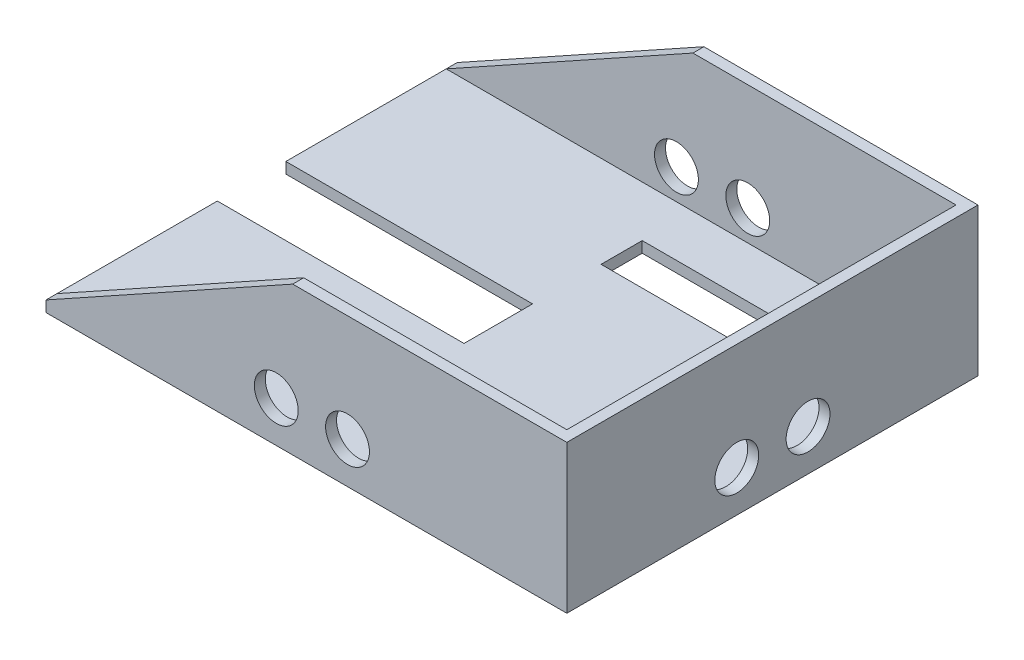
SolidWorks part; units mm, degrees
ref_plane "Front" through (0, 0, 0) normal (0, 0, 1) x (1, 0, 0)
ref_plane "Top" through (0, 0, 0) normal (0, 1, 0) x (1, 0, 0)
ref_plane "Right" through (0, 0, 0) normal (1, 0, 0) x (0, 0, -1)
sketch "Sketch1" plane through (0, 0, 0) normal (0, 1, 0) x (1, 0, 0)
  line L0 (-5, -12.5) -> (-5, 12.5)
  line L1 (95, -75) -> (-95, -75)
  line L2 (95, -75) -> (95, 75)
  line L3 (95, 75) -> (-95, 75)
  line L4 (-95, -75) -> (-95, -12.5)
  line L5 (0, 75) -> (0, -75) construction
  line L6 (95, 0) -> (-95, 0) construction
  line L7 (-5, 12.5) -> (-95, 12.5)
  line L8 (-5, -12.5) -> (-95, -12.5)
  line L9 (-95, 12.5) -> (-95, 75)
  point P0 (0, 0)
  point P4 (0, 0)
  point P7 (-5, 0)
  dimension "D1" = 190
  dimension "D2" = 150
  dimension "D3" = 25
  dimension "D4" = 100
extrude "Boss-Extrude1" add sketch "Sketch1" along normal blind 4
sketch "Sketch2" plane through (0, 0, 75) normal (0, 0, 1) x (1, 0, 0)
  line L0 (95, 4) -> (95, 54)
  line L1 (95, 54) -> (-5, 54)
  line L2 (-5, 54) -> (-95, 4)
  line L3 (-95, 4) -> (95, 4)
  dimension "D1" = 50
  dimension "D2" = 100
extrude "Boss-Extrude2" add sketch "Sketch2" against normal blind 4
mirror "Mirror1" about plane through (0, 0, 0) normal (0, 0, 1) of "Boss-Extrude2"
sketch "Sketch3" plane through (95, 0, 0) normal (1, 0, 0) x (0, 0, -1)
  line L0 (-71, 54) -> (71, 54)
  line L1 (71, 4) -> (71, 54) construction
  line L2 (71, 54) -> (71, 4)
  line L3 (71, 4) -> (-71, 4)
  line L4 (-71, 4) -> (-71, 54)
extrude "Boss-Extrude3" add sketch "Sketch3" against normal blind 4
sketch "Sketch4" plane through (0, 0, 0) normal (0, -1, 0) x (1, 0, 0)
  line L0 (95, 75) -> (95, -75) construction
  line L1 (75, 52.5) -> (-5, 52.5)
  line L2 (75, 52.5) -> (75, 37.5)
  line L3 (75, 37.5) -> (-5, 37.5)
  line L4 (-5, 52.5) -> (-5, 37.5)
  line L5 (35, 37.5) -> (35, 52.5) construction
  line L6 (75, 45) -> (-5, 45) construction
  line L7 (-95, 75) -> (95, 75) construction
  point P0 (35, 45)
  dimension "D1" = 60
  dimension "D2" = 30
  dimension "D3" = 80
  dimension "D4" = 15
extrude "Cut-Extrude1" cut sketch "Sketch4" against normal blind 4 contours L3 L4 L1 L2
mirror "Mirror2" about plane through (0, 0, 0) normal (0, 0, 1) of "Cut-Extrude1"
sketch "Sketch5" plane through (95, 0, 0) normal (1, 0, 0) x (0, 0, -1)
  line L0 (-13, 15) -> (13, 15) construction
  circle A0 centre (-13, 15) radius 8
  circle A1 centre (13, 15) radius 8
  point P2 (0, 15)
  dimension "D1" = 26
  dimension "D2" = 15
  dimension "D3" = 0
extrude "Cut-Extrude2" cut sketch "Sketch5" against normal blind 4
sketch "Sketch6" plane through (0, 0, -75) normal (0, 0, -1) x (-1, 0, 0)
  line L0 (-15, 15) -> (11, 15) construction
  line L1 (-95, 54) -> (-95, 0) construction
  line L2 (-95, 0) -> (95, 0) construction
  circle A0 centre (-15, 15) radius 8
  circle A1 centre (11, 15) radius 8
  dimension "D3" = 15
  dimension "D1" = 26
  dimension "D2" = 80
extrude "Cut-Extrude3" cut sketch "Sketch6" against normal blind 4
mirror "Mirror3" about plane through (0, 0, 0) normal (0, 0, 1) of "Cut-Extrude3"
